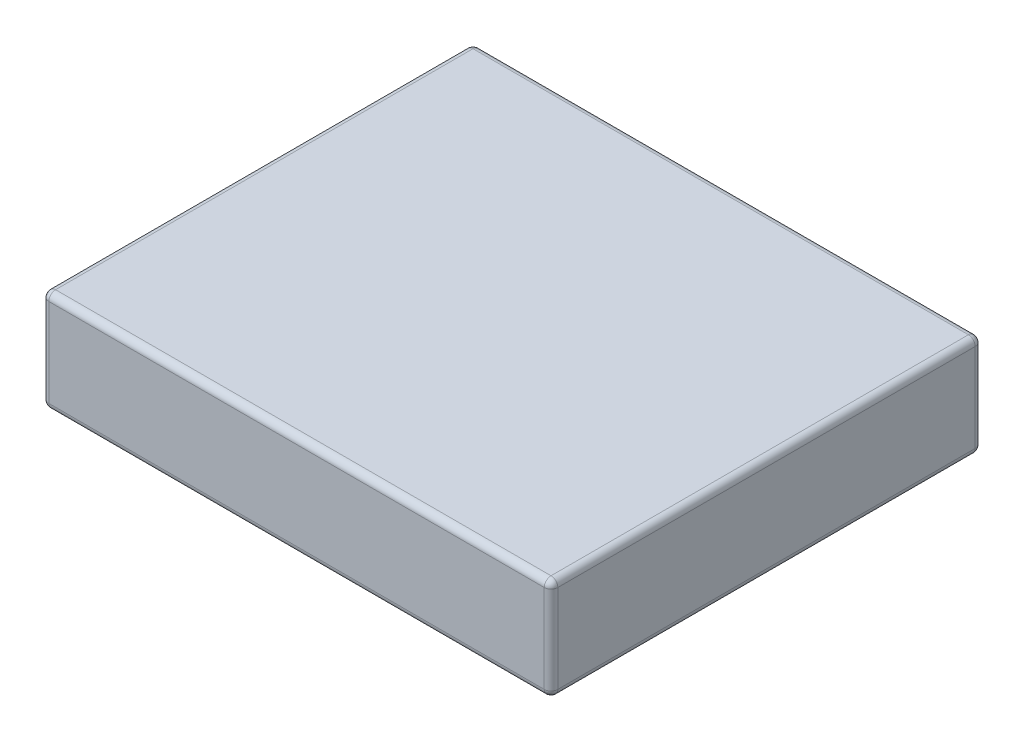
SolidWorks part; units mm, degrees
material "Nickel"
ref_plane "Front Plane" through (0, 0, 0) normal (0, 0, 1) x (1, 0, 0)
ref_plane "Top Plane" through (0, 0, 0) normal (0, 1, 0) x (1, 0, 0)
ref_plane "Right Plane" through (0, 0, 0) normal (1, 0, 0) x (0, 0, -1)
sketch "Sketch1" plane through (0, 0, 0) normal (0, 1, 0) x (1, 0, 0)
  line L1 (-15, 12.7) -> (15, 12.7)
  line L2 (-15, 12.7) -> (-15, -12.7)
  line L3 (-15, -12.7) -> (15, -12.7)
  line L4 (15, 12.7) -> (15, -12.7)
  line L5 (-15, 12.7) -> (15, -12.7) construction
  line L6 (-15, -12.7) -> (15, 12.7) construction
  point P4 (0, 0)
  dimension "D1" = 30
  dimension "D2" = 25.4
extrude "Boss-Extrude1" add sketch "Sketch1" along normal blind 3 and the other way blind 3
fillet "Fillet1" radius 0.4 12 edges at (15, 0, 12.7) (15, 0, -12.7) (-15, 0, -12.7) (-15, 0, 12.7) (0, 3, -12.7) (15, 3, 0) (0, 3, 12.7) (-15, 3, 0) (0, -3, 12.7) (15, -3, 0) (0, -3, -12.7) (-15, -3, 0)
